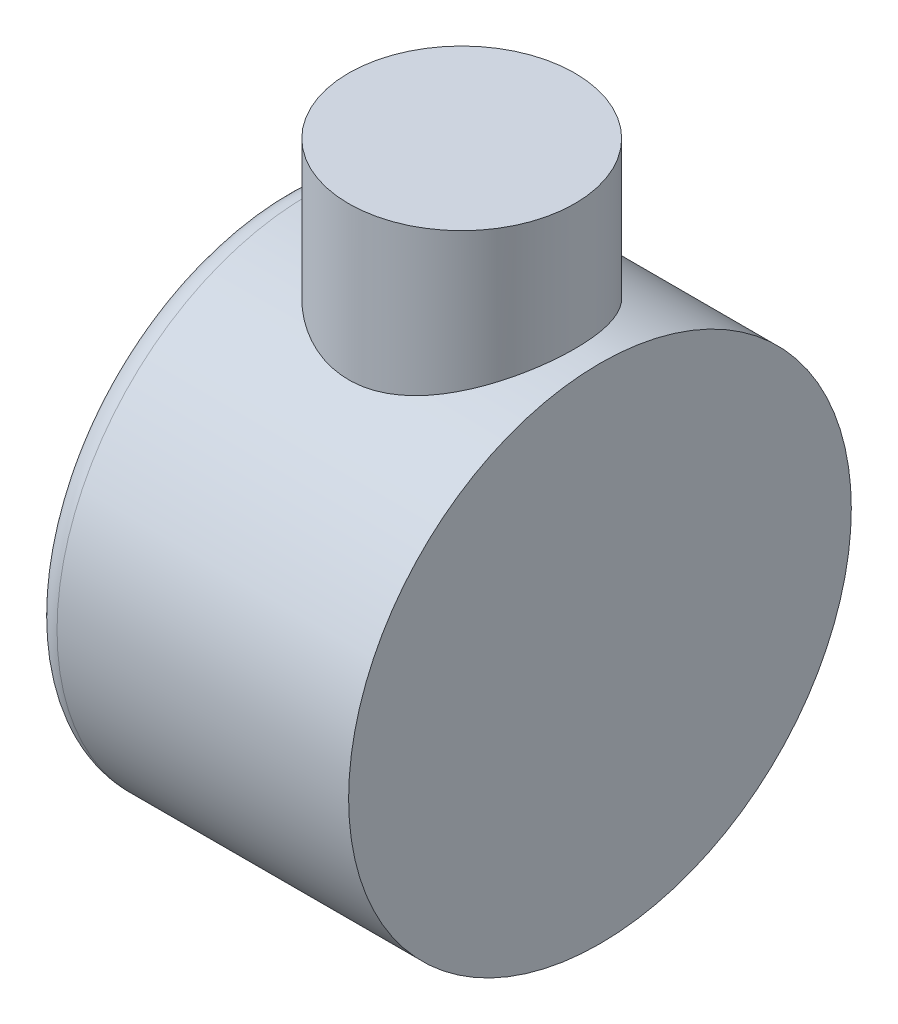
SolidWorks part; units mm, degrees
ref_plane "Front Plane" through (0, 0, 0) normal (0, 0, 1) x (1, 0, 0)
ref_plane "Top Plane" through (0, 0, 0) normal (0, 1, 0) x (1, 0, 0)
ref_plane "Right Plane" through (0, 0, 0) normal (1, 0, 0) x (0, 0, -1)
sketch "Sketch2" plane through (0, 0, 0) normal (1, 0, 0) x (0, 0, -1)
  circle A0 centre (0, 0) radius 50
  dimension "D1" = 100
extrude "Boss-Extrude1" add sketch "Sketch2" along normal blind 55
ref_plane "Plane1" through (27.5, 0, 0) normal (-1, 0, 0) x (0, 0, 1)
sketch "Sketch3" plane through (27.5, 0, 0) normal (-1, 0, 0) x (0, 0, 1)
  line L0 (0, 50) -> (0, 75)
  line L1 (0, 75) -> (22.5, 75)
  line L2 (0, 75) -> (-22.5, 75)
  line L3 (-22.5, 75) -> (-22.5, 44.6514)
  line L4 (22.5, 75) -> (22.5, 44.6514)
  circle A1 centre (0, 0) radius 50
  circle A2 centre (0, 0) radius 50
  dimension "D2" = 25
  dimension "D3" = 22.5
  dimension "D4" = 22.5
  dimension "D1" = 0
revolve "Revolve1" add sketch "Sketch3" angle 360 about L0 region at (27.5, 61.5818, 11.6206)
sketch "Sketch4" plane through (0, 0, 0) normal (-1, 0, 0) x (0, 0, 1)
  circle A1 centre (0, 0) radius 50
  circle A2 centre (0, 0) radius 50
  dimension "D1" = 0
extrude "Boss-Extrude2" add sketch "Sketch4" along normal blind 8
fillet "Fillet1" radius 5 1 edges at (-8, 0, 50)
